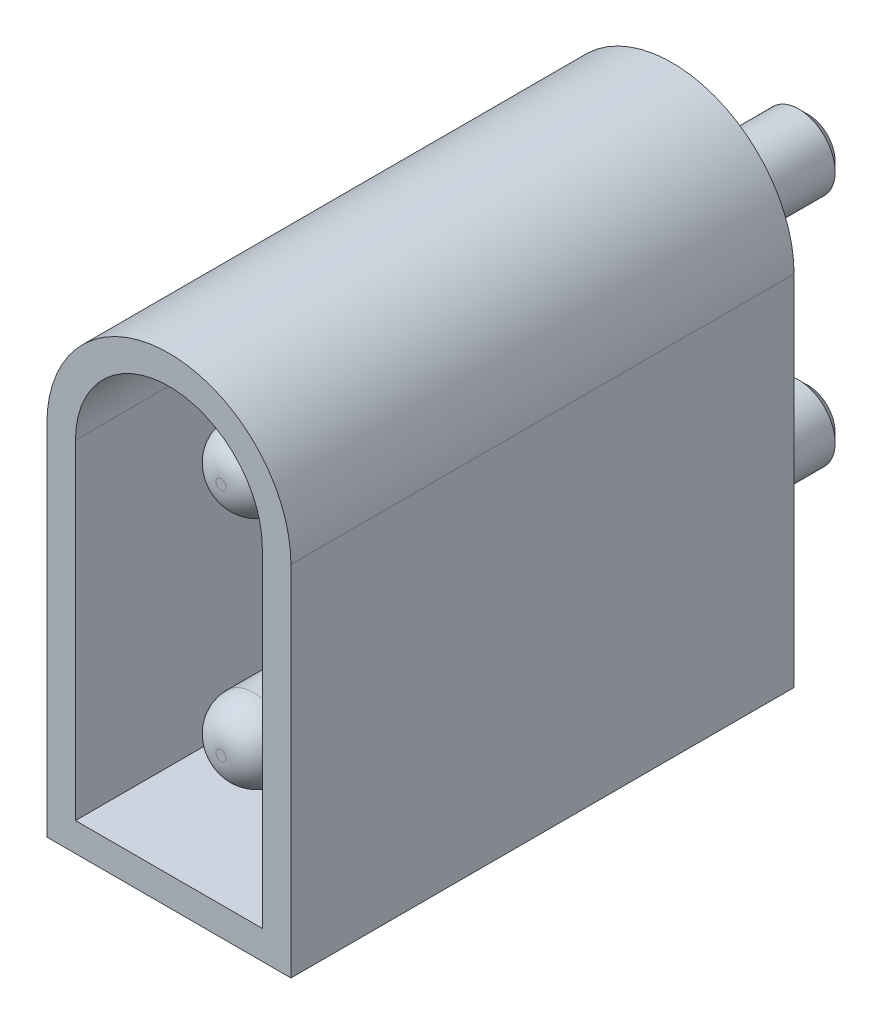
SolidWorks part; units mm, degrees
ref_plane "Alzado" through (0, 0, 0) normal (0, 0, 1) x (1, 0, 0)
ref_plane "Planta" through (0, 0, 0) normal (0, 1, 0) x (1, 0, 0)
ref_plane "Vista lateral" through (0, 0, 0) normal (1, 0, 0) x (0, 0, -1)
sketch "Croquis1" plane through (0, 0, 0) normal (0, 0, 1) x (1, 0, 0)
  line L0 (-2.6, 7.63) -> (-2.6, 0)
  line L1 (-2.6, 0) -> (2.6, 0)
  line L2 (2.6, 0) -> (2.6, 7.63)
  arc A0 (-2.6, 7.63) -> (2.6, 7.63) centre (0, 7.63) cw
  point P4 (0, 0)
  point P7 (0, 10.23)
  dimension "D1" = 5.2
  dimension "D2" = 10.23
extrude "Saliente-Extruir1" add sketch "Croquis1" along normal blind 10.72
sketch "Croquis2" plane through (0, 0, 0) normal (0, 0, -1) x (-1, 0, 0)
  line L0 (2.6, 0) -> (-2.6, 0) construction
  circle A0 centre (0, 7.25) radius 0.775
  circle A1 centre (0, 2.25) radius 0.775
  dimension "D1" = 1.55
  dimension "D2" = 5
  dimension "D3" = 2.25
extrude "Saliente-Extruir2" add sketch "Croquis2" along normal blind 2.9
chamfer "Chaflán1" distance 0.2 angle 45 2 edges at (-0.775, 2.25, -2.9) (-0.775, 7.25, -2.9)
shell "Vaciado1" thickness 0.61 removed face at (0, 4.465, 10.72)
sketch "Croquis4" plane through (0, 0, 0.61) normal (0, 0, 1) x (1, 0, 0)
  circle A0 centre (0, 2.25) radius 0.81
  circle A1 centre (0, 7.25) radius 0.81
  dimension "D1" = 1.62
extrude "Saliente-Extruir4" add sketch "Croquis4" along normal blind 9
fillet "Redondeo1" radius 0.7 2 edges at (0.81, 7.25, 9.61) (0.81, 2.25, 9.61)
